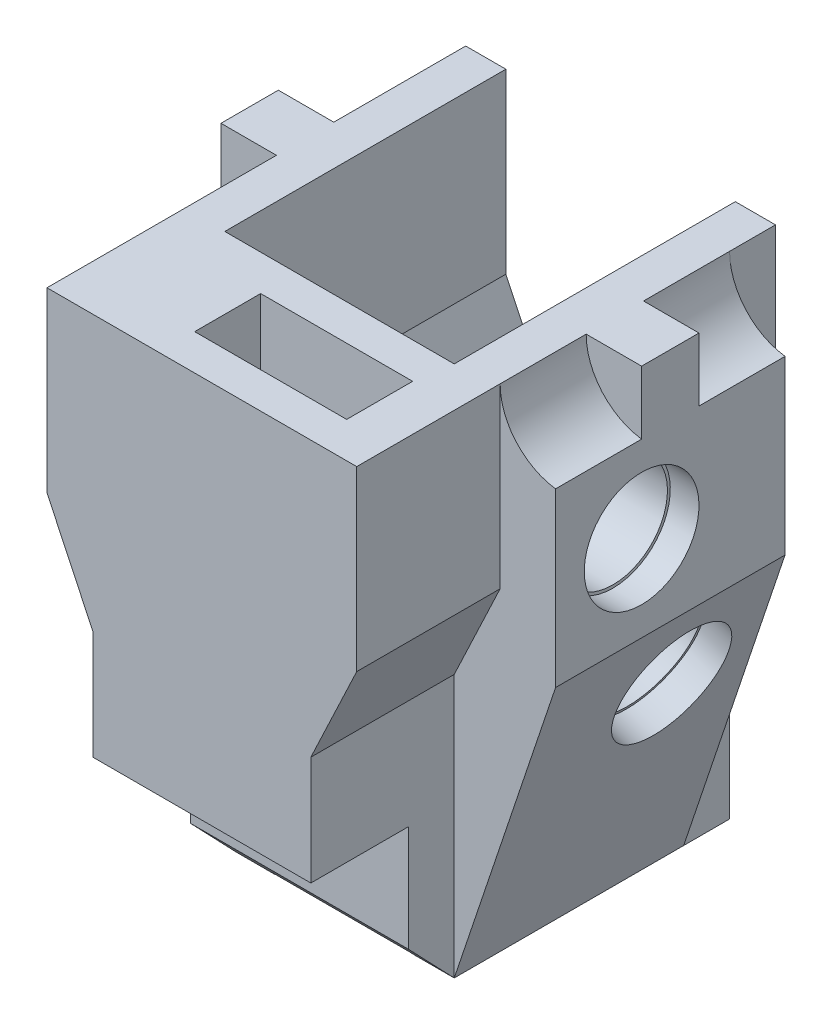
SolidWorks part; units mm, degrees
note: The reader was unsure of these and kept them because the rebuilt part matched: shared geometry of "Sketch4<4>", "Sketch5<3>", "Sketch21<3>", "Sketch21<4>".
ref_plane "Front Plane" through (0, 0, 0) normal (0, 0, 1) x (1, 0, 0)
ref_plane "Top Plane" through (0, 0, 0) normal (0, 1, 0) x (1, 0, 0)
ref_plane "Right Plane" through (0, 0, 0) normal (1, 0, 0) x (0, 0, -1)
sketch "Sketch1" plane through (0, 0, 0) normal (0, 0, 1) x (1, 0, 0)
  line L0 (0, 0) -> (-1.2, 0) construction
  line L1 (-1.2, 0) -> (-1.9, 0)
  line L2 (-1.9, 0) -> (-1.9, 4.5838)
  line L3 (-1.9, 4.5838) -> (-2.7, 6.2762)
  line L4 (-2.7, 6.2762) -> (-2.7, 19.5073)
  line L5 (-2.7, 19.5073) -> (-2, 19.5073)
  line L6 (-2, 19.5073) -> (-2, 6.2762)
  line L7 (-2, 6.2762) -> (-1.2, 4.5838)
  line L8 (-1.2, 4.5838) -> (-1.2, 0)
  line L9 (-1.9, 0) -> (-3.6666, 5.2688) construction
  line L10 (-3.6666, 5.2688) -> (-3.6666, 8.2688) construction
  line L11 (-3.6666, 8.2688) -> (-2.7, 9.3712) construction
  line L12 (-2.7, 9.3712) -> (-2.7, 6.2762) construction
  line L13 (-2.7, 6.2762) -> (-1.9, 4.5838) construction
  line L14 (-1.9, 4.5838) -> (-1.9, 0) construction
  arc A0 (-3.6666, 8.2688) -> (-2.7, 9.3712) centre (-3.8119, 9.3712) ccw construction
  dimension "D9" = 1.1119
  dimension "D1" = 0.7
  dimension "D2" = 2
  dimension "D3" = 154.7
  dimension "D5" = 19.5073
  dimension "D6" = 1.2
  dimension "D7" = 3.095
  dimension "D8" = 3
  dimension "D10" = 18.536
  dimension "D11" = 0.9666
extrude "Boss-Extrude1" add sketch "Sketch1" along normal blind 5.6
ref_plane "Plane1" through (0, 0, 2.8) normal (0, 0, 1) x (1, 0, 0)
sketch "Sketch3" plane through (0, 0, 2.8) normal (0, 0, 1) x (1, 0, 0)
  line L0 (-1.9, 0) -> (-3.6666, 5.2688)
  line L1 (-3.6666, 5.2688) -> (-3.6666, 8.2688)
  line L2 (-3.6666, 8.2688) -> (-2.7, 9.3712) construction
  line L3 (-2.7, 19.5073) -> (-2.7, 6.2762) construction
  line L4 (-2.7, 9.3712) -> (-2.7, 6.2762)
  line L5 (-2.7, 6.2762) -> (-1.9, 4.5838)
  line L6 (-1.9, 4.5838) -> (-1.9, 0)
  arc A0 (-3.6666, 8.2688) -> (-2.7, 9.3712) centre (-3.8119, 9.3712) ccw
  dimension "D1" = 0.9666
  dimension "D2" = 3
  dimension "D3" = 3.095
  dimension "D4" = 18.536
extrude "Boss-Extrude2" add sketch "Sketch3" along normal blind 2 and the other way blind 2
sketch "Sketch4" plane through (-3.6666, 0, 0) normal (-1, 0, 0) x (0, 0, 1)
  line L0 (3.3, 6.7688) -> (4.8, 6.7688) construction
  line L2 (3.3, 6.7688) -> (3.3, 8.2688) construction
  line L4 (4.8, 8.2688) -> (4.8, 5.2688) construction
  line L5 (0.8, 8.2688) -> (4.8, 8.2688) construction
  circle A0 centre (3.3, 6.7688) radius 1
  circle A1 centre (3.3, 6.7688) radius 0.95
  dimension "D1" = 2
  dimension "D2" = 1.9
  dimension "D3" = 1.5
  dimension "D4" = 1.5
extrude "Cut-Extrude1" cut sketch "Sketch4" against normal blind 1.5 contours A1
extrude "Cut-Extrude2" cut sketch "Sketch4<4>" against normal blind 0.5 contours A0
sketch "Sketch4<4>" plane through (-3.6666, 0, 0) normal (-1, 0, 0) x (0, 0, 1) same geometry as "Sketch4"
sketch "Sketch5" plane through (-1.708, -0.5727, 0) normal (-0.9481, -0.3179, 0) x (0, 0, 1)
  line L0 (2.3, 6.1611) -> (2.3, 4.6611) construction
  line L1 (0.8, 6.1611) -> (4.8, 6.1611) construction
  line L2 (2.3, 4.6611) -> (0.8, 4.6611) construction
  line L3 (0.8, 6.1611) -> (0.8, 0.604) construction
  circle A0 centre (2.3, 4.6611) radius 1
  circle A1 centre (2.3, 4.6611) radius 0.95
  dimension "D1" = 2
  dimension "D2" = 1.9
  dimension "D3" = 1.5
  dimension "D4" = 1.5
extrude "Cut-Extrude3" cut sketch "Sketch5" against normal blind 1.5 contours A1
extrude "Cut-Extrude4" cut sketch "Sketch5<3>" against normal blind 0.5 contours A0
sketch "Sketch5<3>" plane through (-1.708, -0.5727, 0) normal (-0.9481, -0.3179, 0) x (0, 0, 1) same geometry as "Sketch5"
sketch "Sketch6" plane through (0, 19.5073, 0) normal (0, 1, 0) x (1, 0, 0)
  line L0 (-2.7, -5.6) -> (-2.7, 0) construction
  line L1 (-2.7, -2.3) -> (-3.6666, -2.3)
  line L2 (-2.7, -2.3) -> (-2.7, -3.3)
  line L3 (-2.7, -3.3) -> (-3.6666, -3.3)
  line L4 (-3.6666, -2.3) -> (-3.6666, -3.3)
  line L5 (-3.6666, -0.8) -> (-3.6666, -4.8) construction
  line L6 (-2.7, -0.8) -> (-2.7, -4.8) construction
  point P8 (-2.7, -2.8)
  dimension "D1" = 1
extrude "Boss-Extrude3" add sketch "Sketch6" against normal up to next
sketch "Sketch7" plane through (-1.2, 0, 0) normal (1, 0, 0) x (0, 0, -1)
  line L0 (-5.6, 4.5838) -> (-5.6, 0)
  line L1 (-5.6, 0) -> (-5.1828, 0)
  line L2 (-5.6, 0) -> (0, 0) construction
  line L3 (-5.1828, 0) -> (-5.6, 4.5838)
  line L4 (0, 4.5838) -> (0, 0)
  line L5 (0, 0) -> (-0.4172, 0)
  line L6 (-0.4172, 0) -> (0, 4.5838)
  dimension "D1" = 95.2
extrude "Cut-Extrude5" [suppressed] cut sketch "Sketch7" against normal up to next
mirror "Mirror7" about plane through (0, 0, 0) normal (1, 0, 0) of bodies 107 108
sketch "Sketch8" plane through (0, 0, 0) normal (1, 0, 0) x (0, 0, -1)
  line L0 (-5.6, 4.5838) -> (0, 4.5838) construction
  line L1 (-5.6, 0) -> (-4.9, 0)
  line L2 (-5.6, 0) -> (-5.6, 4.5838)
  line L3 (-5.6, 4.5838) -> (-4.9, 4.5838)
  line L4 (-4.9, 0) -> (-4.9, 4.5838)
  dimension "D1" = 0.7
extrude "Boss-Extrude4" add sketch "Sketch8" along normal up to next and the other way up to next
sketch "Sketch9" plane through (0, 0, 0) normal (1, 0, 0) x (0, 0, -1)
  line L0 (-5.5824, 1.0186) -> (-4.8, 0.2013)
  line L2 (-4.9, 0) -> (-4.9, 4.5838) construction
  line L3 (-4.8, 0.2013) -> (-4.8, -0.5287)
  line L4 (-4.8, -0.5287) -> (-5.5824, 0.2886)
  line L5 (-5.5824, 0.2886) -> (-5.5824, 1.0186)
  line L6 (-4.8, 5.2688) -> (-4.8, 0) construction
  dimension "D1" = 0.73
  dimension "D2" = 136.25
sketch "Sketch10" plane through (0, 0, 0) normal (1, 0, 0) x (0, 0, -1)
  line L0 (-4.9, 4.5838) -> (0, 4.5838) construction
  line L1 (-5.6, 19.5073) -> (-4.9, 19.5073)
  line L2 (-5.6, 19.5073) -> (-5.6, 4.5838)
  line L3 (-5.6, 4.5838) -> (-4.9, 4.5838)
  line L4 (-4.9, 19.5073) -> (-4.9, 4.5838)
  line L5 (-4.9, 0) -> (-4.9, 4.5838) construction
extrude "Boss-Extrude5" add sketch "Sketch10" along normal up to next and the other way up to next
sketch "Sketch12" plane through (0, 0, 4.9) normal (0, 0, -1) x (-1, 0, 0)
  line L0 (-2, 19.5073) -> (-0.5858, 18.0931) construction
  line L1 (-2, 6.2762) -> (-2, 19.5073) construction
  line L2 (0, 55) -> (0, -55) construction
  circle A0 centre (-0.5858, 18.0931) radius 0.75
  circle A1 centre (-0.5858, 14.0931) radius 0.75
  circle A2 centre (-0.5858, 10.0931) radius 0.75
  circle A3 centre (0.5858, 10.0931) radius 0.75
  circle A4 centre (0.5858, 14.0931) radius 0.75
  circle A5 centre (0.5858, 18.0931) radius 0.75
  dimension "D2" = 1.5
  dimension "D1" = 2
  dimension "D3" = 45
  dimension "D5" = 4
  dimension "D4" = 3
extrude "Cut-Extrude7" [suppressed] cut sketch "Sketch12" against normal up to next
sketch "Sketch13" plane through (0, 0, 5.6) normal (0, 0, 1) x (1, 0, 0)
  line L0 (3.6666, 8.2688) -> (3.6666, 19.5073) construction
  line L1 (-3.6666, 19.5073) -> (3.6666, 19.5073)
  line L2 (-3.6666, 19.5073) -> (-3.6666, 12.6073)
  line L3 (-3.6666, 12.6073) -> (3.6666, 12.6073)
  line L4 (3.6666, 19.5073) -> (3.6666, 12.6073)
  dimension "D1" = 6.9
extrude "Cut-Extrude8" cut sketch "Sketch13" against normal through all
extrude "Boss-Extrude6" add sketch "Sketch9" along normal up to surface and the other way up to surface up to face at (1.9, 2.2919, 5.2) other way up to face at (-1.9, 2.2919, 5.2)
sketch "Sketch14" plane through (0, 0, 0) normal (0, -1, 0) x (1, 0, 0)
  line L0 (-1.9, 0) -> (-1.2, 0) construction
  line L1 (-1.22, 0) -> (1.22, 0)
  line L2 (-1.22, 0) -> (-1.22, 4.8)
  line L3 (-1.22, 4.8) -> (1.22, 4.8)
  line L4 (1.22, 0) -> (1.22, 4.8)
  line L5 (1.2, 4.8) -> (1.9, 4.8) construction
  line L6 (-1.2, 4.8) -> (-1.2, 0) construction
  line L7 (1.2, 4.8) -> (1.2, 0) construction
  dimension "D1" = 0.02
  dimension "D2" = 0.02
extrude "Cut-Extrude9" cut sketch "Sketch14" against normal up to next
sketch "Sketch15" plane through (0, 0, 0) normal (0, 0, 1) x (1, 0, 0)
  line L0 (-1.9, 0) -> (-4.75, 8.4999)
  line L1 (-4.75, 8.4999) -> (-4.75, 11.4999)
  line L2 (-4.75, 11.4999) -> (-3.7834, 12.6023) construction
  line L4 (-3.7834, 12.6023) -> (-3.7834, 9.5073)
  line L5 (-3.7834, 9.5073) -> (-1.9, 5.523)
  line L6 (-1.9, 5.523) -> (-1.9, 0)
  arc A0 (-4.75, 11.4999) -> (-3.7834, 12.6023) centre (-4.8953, 12.6023) ccw
  dimension "D1" = 0.9666
  dimension "D2" = 3
  dimension "D3" = 3.095
  dimension "D4" = 18.536
sketch "Sketch16" plane through (0, 0, 5.6) normal (0, 0, 1) x (1, 0, 0)
  line L0 (-2.7, 12.6073) -> (2.7, 12.6073)
  line L1 (2.7, 12.6073) -> (2.7, 6.2762)
  line L2 (2.7, 6.2762) -> (1.9, 4.5838)
  line L3 (1.9, 4.5838) -> (1.9, 2.8338)
  line L4 (1.9, 2.8338) -> (-1.9, 2.8338)
  line L5 (-1.9, 2.8338) -> (-1.9, 4.5838)
  line L6 (-1.9, 4.5838) -> (-2.7, 6.2762)
  line L7 (-2.7, 6.2762) -> (-2.7, 12.6073)
  line L8 (-2.7, 12.6073) -> (-2.7, 6.2762) construction
  line L10 (1.9, 4.5838) -> (1.9, 0) construction
  line L12 (-2.7, 12.6073) -> (2.7, 12.6073) construction
  line L13 (-2.7, 6.2762) -> (-2.7, 9.3712) construction
  dimension "D2" = 1.75
extrude "Boss-Extrude7" add sketch "Sketch16" along normal blind 1.7
sketch "Sketch17" plane through (-1.9, 0, 0) normal (-1, 0, 0) x (0, 0, 1)
  line L0 (4.8, -0.5287) -> (4.8, 0)
  line L1 (4.8, 0) -> (5.6, 0.8357)
  line L2 (5.6, 2.8338) -> (5.6, 0) construction
  line L3 (5.6, 0.8357) -> (5.6, 0)
  line L4 (5.6, 0) -> (5.3061, 0)
  line L5 (5.3061, 0) -> (4.8, -0.5287)
extrude "Cut-Extrude10" cut sketch "Sketch17" against normal through all
sketch "Sketch18" plane through (0, 12.6073, 0) normal (0, 1, 0) x (1, 0, 0)
  line L0 (1.2, -4.9) -> (2, -4.9) construction
  line L1 (-1.22, -4.8) -> (1.22, -4.8)
  line L2 (-1.22, -4.8) -> (-1.22, -4.9)
  line L3 (-1.22, -4.9) -> (1.22, -4.9)
  line L4 (1.22, -4.8) -> (1.22, -4.9)
  line L5 (1.2, -4.8) -> (-1.2, -4.8) construction
  line L8 (1.22, -4.8) -> (1.22, 0) construction
extrude "Cut-Extrude11" cut sketch "Sketch18" against normal through all
sketch "Sketch20" plane through (0, 0, 7.3) normal (0, 0, 1) x (1, 0, 0)
  line L0 (-3.6666, 8.2688) -> (-3.6666, 12.6073) construction
  line L1 (-3.6666, 9.3712) -> (3.6666, 9.3712)
  line L2 (-3.6666, 9.3712) -> (-3.6666, 12.6073)
  line L3 (-3.6666, 12.6073) -> (3.6666, 12.6073)
  line L4 (3.6666, 9.3712) -> (3.6666, 12.6073)
extrude "Cut-Extrude12" cut sketch "Sketch20" against normal through all both
sketch "Sketch21" plane through (-2.7, 0, 0) normal (-1, 0, 0) x (0, 0, 1)
  line L0 (4.8, 6.2762) -> (7.3, 9.3712) construction
  circle A0 centre (6.05, 7.8237) radius 1.0003
  circle A1 centre (6.05, 7.8237) radius 0.95
  circle A2 centre (6.05, 7.8237) radius 0.55
  dimension "D1" = 2.0007
  dimension "D2" = 1.1
  dimension "D3" = 1.9
extrude "Cut-Extrude13" cut sketch "Sketch21" against normal blind 2.5 contours A2 L0 | L0 A2
extrude "Cut-Extrude14" cut sketch "Sketch21<3>" against normal blind 1.5 contours A1
sketch "Sketch21<3>" plane through (-2.7, 0, 0) normal (-1, 0, 0) x (0, 0, 1) same geometry as "Sketch21"
extrude "Cut-Extrude15" cut sketch "Sketch21<4>" against normal blind 0.5 contours A0
sketch "Sketch21<4>" plane through (-2.7, 0, 0) normal (-1, 0, 0) x (0, 0, 1) same geometry as "Sketch21"
sketch "Sketch22" plane through (0, 9.3712, 0) normal (0, 1, 0) x (1, 0, 0)
  line L0 (-2.7, -7.3) -> (2.7, -4.9) construction
  line L1 (2.7, -4.8) -> (2.7, -7.3) construction
  line L2 (2, -4.9) -> (-2, -4.9) construction
  line L3 (0, -6.1) -> (0.575, -6.1) construction
  line L4 (-0.75, -6.675) -> (1.9, -6.675)
  line L5 (-0.75, -6.675) -> (-0.75, -5.525)
  line L6 (-0.75, -5.525) -> (1.9, -5.525)
  line L7 (1.9, -6.675) -> (1.9, -5.525)
  line L8 (-0.75, -6.675) -> (1.9, -5.525) construction
  line L9 (-0.75, -5.525) -> (1.9, -6.675) construction
  point P8 (0, -6.1)
  dimension "D1" = 2.65
  dimension "D2" = 1.15
  dimension "D3" = 0.8
extrude "Cut-Extrude16" cut sketch "Sketch22" against normal blind 3.6
sketch "Sketch28" plane through (0, 2.8338, 0) normal (0, -1, 0) x (1, 0, 0)
  line L1 (-1.9, 7.3) -> (1.9, 7.3)
  line L2 (-1.9, 7.3) -> (-1.9, 5.6)
  line L3 (-1.9, 5.6) -> (1.9, 5.6)
  line L4 (1.9, 7.3) -> (1.9, 5.6)
extrude "Boss-Extrude10" add sketch "Sketch28" along normal blind 0.15
sketch "Sketch29" [suppressed] plane through (0, 9.3712, 0) normal (0, 1, 0) x (1, 0, 0)
  line L0 (2, -4.9) -> (2, 0) construction
  line L1 (-2, -4.9) -> (2, -4.9)
  line L2 (0, -4.9) -> (0, -5.9) construction
  arc A0 (-2, -4.9) -> (2, -4.9) centre (0, -3.4) ccw
  dimension "D1" = 1
